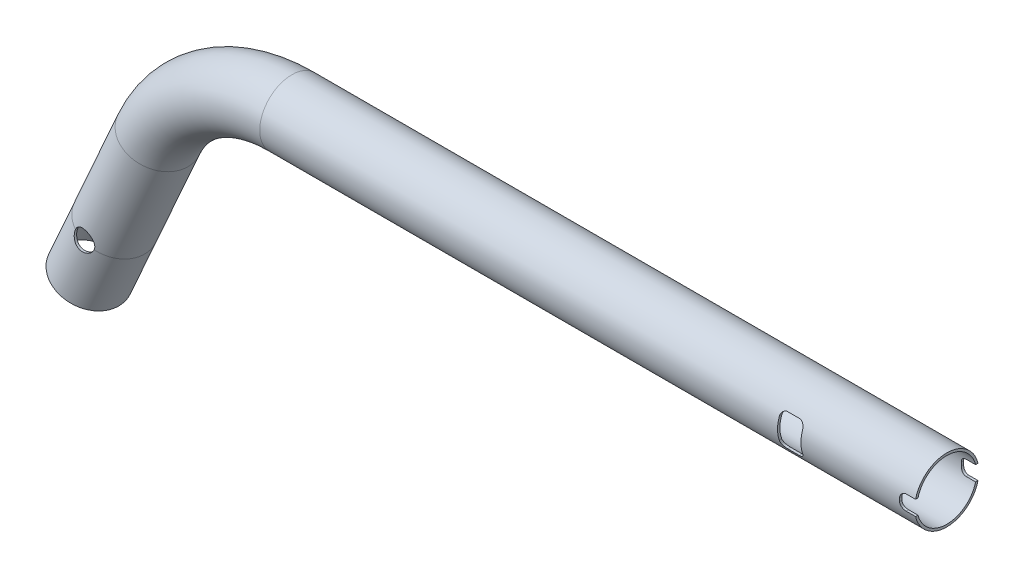
SolidWorks part; units mm, degrees
ref_plane "Front Plane" through (0, 0, 0) normal (0, 0, 1) x (1, 0, 0)
ref_plane "Top Plane" through (0, 0, 0) normal (0, 1, 0) x (1, 0, 0)
ref_plane "Right Plane" through (0, 0, 0) normal (1, 0, 0) x (0, 0, -1)
sketch "Sketch1" plane through (0, 0, 0) normal (0, 0, 1) x (1, 0, 0)
  line L0 (-90.7401, 0) -> (90.7401, 0)
  line L1 (-136.4174, -29.6632) -> (-151.2599, -63)
  line L2 (90.7401, 0) -> (133.7401, 0)
  line L3 (-151.2599, -63) -> (-160.0909, -82.8347)
  arc A0 (-90.7401, 0) -> (-136.4174, -29.6632) centre (-90.7401, -50) ccw
  point P4 (0, 0)
  point P10 (-151.2599, -63)
  dimension "D2" = 50
  dimension "D7" = 242
  dimension "D4" = 21.7118
  dimension "D1" = 66
  dimension "D3" = 63
  dimension "D5" = 43
  dimension "D6" = 66
ref_plane "Plane1" through (90.7401, 0, 0) normal (1, 0, 0) x (0, 0, -1)
sketch "Sketch3" plane through (90.7401, 0, 0) normal (1, 0, 0) x (0, 0, -1)
  circle A0 centre (0, 0) radius 11
  circle A1 centre (0, 0) radius 10.2
  dimension "D1" = 0.8
  dimension "D2" = 22
sweep "Sweep2" add profiles "Sketch3" path "Sketch1"
ref_axis "Axis1" through (133.7401, 0, 0) along (-1, 0, 0)
ref_axis "Axis2" through (-133.0925, -22.1953, 0) along (-0.4067, -0.9135, 0)
sketch "Sketch4" plane through (0, 0, 0) normal (0, 0, 1) x (1, 0, 0)
  line L0 (-161.3089, -58.5259) -> (-141.2109, -67.4741) construction
  line L1 (90.7401, -101.4635) -> (90.7401, 101.4635) construction
  line L2 (133.7401, 0) -> (90.7401, 0) construction
  line L3 (133.7401, -11) -> (133.7401, 11) construction
  line L4 (133.7401, 0) -> (-90.7401, 0) construction
  line L6 (88.7401, -5.5) -> (92.7401, -5.5)
  line L7 (86.7401, -3.5) -> (86.7401, 3.5)
  line L8 (88.7401, 5.5) -> (92.7401, 5.5)
  line L9 (94.7401, -3.5) -> (94.7401, 3.5)
  line L10 (86.7401, -5.5) -> (94.7401, 5.5) construction
  line L11 (86.7401, 5.5) -> (94.7401, -5.5) construction
  circle A0 centre (-151.2599, -63) radius 3.5
  arc A1 (88.7401, -5.5) -> (86.7401, -3.5) centre (88.7401, -3.5) cw
  arc A2 (94.7401, -3.5) -> (92.7401, -5.5) centre (92.7401, -3.5) cw
  arc A3 (92.7401, 5.5) -> (94.7401, 3.5) centre (92.7401, 3.5) cw
  arc A4 (88.7401, 5.5) -> (86.7401, 3.5) centre (88.7401, 3.5) ccw
  dimension "D1" = 43
  dimension "D4" = 2
  dimension "D6" = 7
  dimension "D2" = 8
  dimension "D3" = 11
extrude "Cut-Extrude1" cut sketch "Sketch4" along normal up to next
sketch "Sketch5" plane through (0, 0, 0) normal (0, 0, 1) x (1, 0, 0)
  line L0 (-160.5781, -58.8513) -> (-141.9417, -67.1487) construction
  circle A0 centre (-151.2599, -63) radius 3.3
extrude "Cut-Extrude2" cut sketch "Sketch5" against normal through all
sketch "Sketch6" plane through (0, 0, 0) normal (0, 0, 1) x (1, 0, 0)
  line L4 (133.8139, 2.5547) -> (133.7401, -2.5547)
  line L5 (133.7401, -11) -> (133.7401, 11) construction
  line L6 (133.7401, -2.5547) -> (130.5401, -2.5547)
  line L7 (128.5401, -0.5547) -> (128.5401, 0.5547)
  line L8 (130.5401, 2.5547) -> (133.8139, 2.5547)
  arc A2 (130.5401, -2.5547) -> (128.5401, -0.5547) centre (130.5401, -0.5547) cw
  arc A3 (130.5401, 2.5547) -> (128.5401, 0.5547) centre (130.5401, 0.5547) ccw
  point P7 (133.777, 0)
  point P11 (128.5401, -2.5547)
  dimension "D1" = 5.11
  dimension "D3" = 2
  dimension "D2" = 5.2
extrude "Cut-Extrude3" cut sketch "Sketch6" against normal through all and the other way through all
